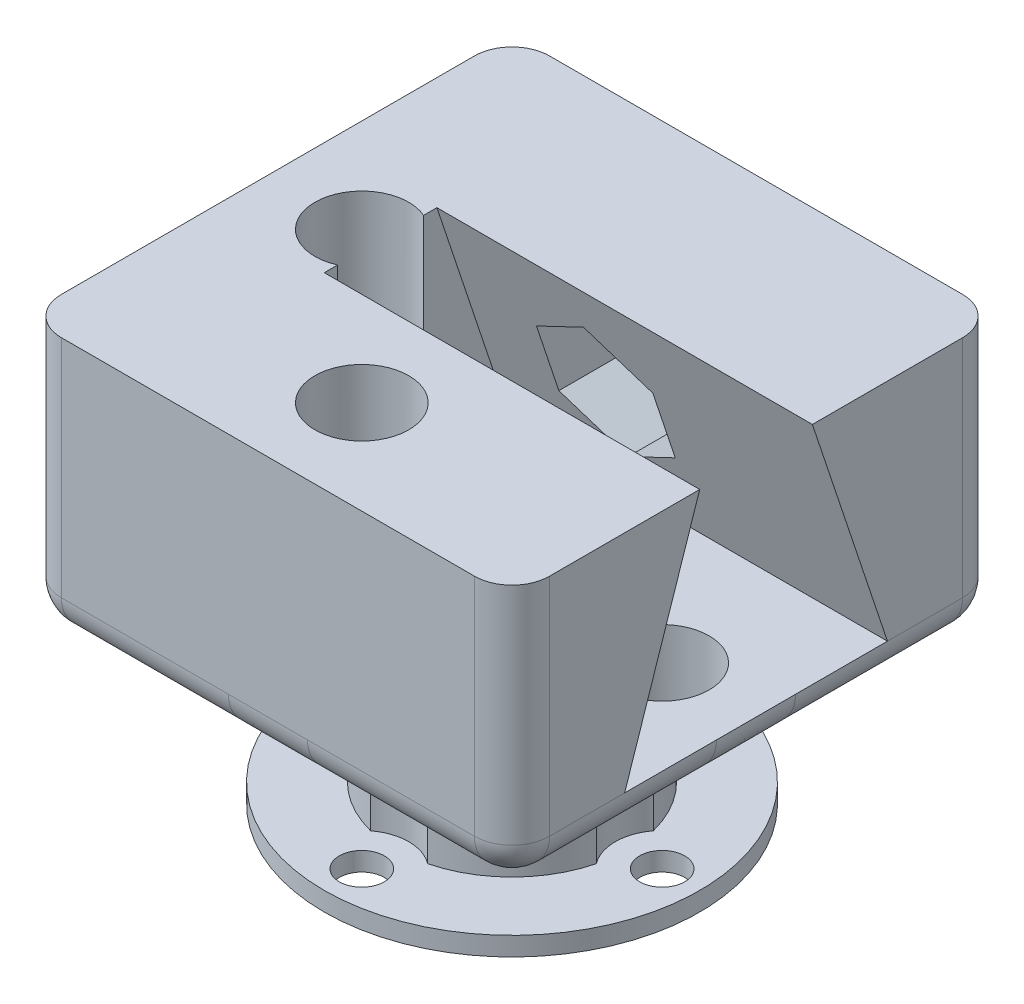
SolidWorks part; units mm, degrees
material "ABS"
ref_plane "Plan de face" through (0, 0, 0) normal (0, 0, 1) x (1, 0, 0)
ref_plane "Plan de dessus" through (0, 0, 0) normal (0, 1, 0) x (1, 0, 0)
ref_plane "Plan de droite" through (0, 0, 0) normal (1, 0, 0) x (0, 0, -1)
ref_axis "Axis1" through (0, 33.075, 0) along (0, -1, 0)
sketch "Sketch1" plane through (0, 0, 0) normal (0, 0, 1) x (1, 0, 0)
  line L0 (0, 0) -> (10, 0)
  line L2 (0, 0) -> (0, 8.5)
  line L3 (0, 8.5) -> (6.2, 8.5)
  line L4 (6.2, 1) -> (6.2, 8.5)
  line L5 (6.2, 1) -> (10, 1)
  line L8 (10, 1) -> (10, 0)
  dimension "D1" = 10
  dimension "D2" = 8.5
  dimension "D3" = 1
  dimension "D4" = 6.2
revolve "Revolve1" add sketch "Sketch1" angle 360 about axis through (0, 33.075, 0) along (0, -1, 0)
hole_wizard "M2 Clearance Hole1" positions "Sketch2" profile "Sketch3" hole size "M2" standard "ANSI Metric" end condition up to next
sketch "Sketch2" plane through (0, 1, 0) normal (0, 1, 0) x (1, 0, 0)
  point P0 (-8, 0)
  point P2 (8, 0)
  point P4 (0, 8)
  point P6 (0, -8)
  dimension "D1" = 16
  dimension "D2" = 16
  dimension "D3" = 8
  dimension "D4" = 8
  dimension "D5" = 8
  dimension "D6" = 8
sketch "Sketch3" plane through (-8, 1, 0) normal (1, 0, 0) x (0, 0, 1)
  line L0 (0, 0) -> (0, 1)
  line L1 (0, 1) -> (1.2, 1)
  line L2 (1.2, 1) -> (1.2, 0)
  line L5 (1.2, 0) -> (0, 0)
  line L11 (0, -6.35) -> (0, 107.95) construction
  dimension "Thru Hole Dia." = 2.4
  dimension "Thru Hole Depth" = 1
sketch "Sketch5" plane through (0, 8.5, 0) normal (0, 1, 0) x (1, 0, 0)
  line L1 (13, 13) -> (-13, 13)
  line L2 (13, 13) -> (13, -13)
  line L3 (13, -13) -> (-13, -13)
  line L4 (-13, 13) -> (-13, -13)
  dimension "D1" = 26
  dimension "D2" = 26
  dimension "D3" = 13
  dimension "D4" = 13
extrude "Boss-Extrude1" add sketch "Sketch5" along normal blind 14
sketch "Sketch6" plane through (13, 0, 0) normal (1, 0, 0) x (0, 0, -1)
  line L1 (-13, 22.5) -> (13, 22.5) construction
  line L5 (3, 22.5) -> (-3, 22.5)
  line L9 (-3, 22.5) -> (-7, 10.5)
  line L10 (-7, 10.5) -> (7, 10.5)
  line L11 (7, 10.5) -> (3, 22.5)
  line L12 (13, 22.5) -> (13, 8.5) construction
  line L13 (-13, 22.5) -> (-13, 8.5) construction
  line L14 (-6.2, 8.5) -> (6.2, 8.5) construction
  dimension "D1" = 14
  dimension "D2" = 10
  dimension "D3" = 10
  dimension "D4" = 6
  dimension "D5" = 2
extrude "Cut-Extrude1" cut sketch "Sketch6" against normal blind 20
hole_wizard "M3 Clearance Hole1" positions "Sketch8" profile "Sketch7" hole size "M3" standard "ANSI Metric"
sketch "Sketch8" plane through (0, 0, -13) normal (0, 0, -1) x (-1, 0, 0)
  line L0 (-13, 22.5) -> (13, 22.5) construction
  line L1 (0, 33.075) -> (0, -1.575) construction
  point P0 (0, 16.5)
  dimension "D1" = 6
  dimension "D2" = 0
sketch "Sketch7" plane through (0, 16.5, -13) normal (1, 0, 0) x (0, 1, 0)
  line L0 (0, 0) -> (0, 8)
  line L1 (0, 8) -> (1.8, 8)
  line L2 (1.8, 8) -> (1.8, 0)
  line L5 (1.8, 0) -> (0, 0)
  line L11 (0, -6.35) -> (0, 107.95) construction
  dimension "Thru Hole Dia." = 3.6
  dimension "Thru Hole Depth" = 8
sketch "Sketch9" plane through (0, 0, -13) normal (0, 0, -1) x (-1, 0, 0)
  line L1 (0, 12.9204) -> (3.1, 14.7102)
  line L2 (3.1, 14.7102) -> (3.1, 18.2898)
  line L3 (3.1, 18.2898) -> (0, 20.0796)
  line L4 (0, 20.0796) -> (-3.1, 18.2898)
  line L5 (-3.1, 18.2898) -> (-3.1, 14.7102)
  line L6 (-3.1, 14.7102) -> (0, 12.9204)
  circle A0 centre (0, 16.5) radius 3.1 construction
  dimension "D1" = 6.2
extrude "Cut-Extrude2" cut sketch "Sketch9" against normal up to next from offset 3 offset against normal yes
fillet "Fillet1" radius 5 1 edges at (0, 8.5, 6.2)
sketch "Sketch10" plane through (0, 0, 0) normal (0, -1, 0) x (1, 0, 0)
  circle A0 centre (0, 8) radius 2.5
  dimension "D1" = 5
extrude "Cut-Extrude3" cut sketch "Sketch10" against normal through all from offset 1 offset against normal yes
pattern_circular "CirPattern1" count 2 every 90 about axis through (0, 33.075, 0) along (0, -1, 0) of "Cut-Extrude3"
fillet "Fillet2" radius 2 8 edges at (13, 15.5, -13) (-13, 15.5, -13) (-13, 15.5, 13) (-13, 8.5, 0) (0, 8.5, -13) (0, 8.5, 13) (13, 15.5, 13) (13, 8.5, 0)
